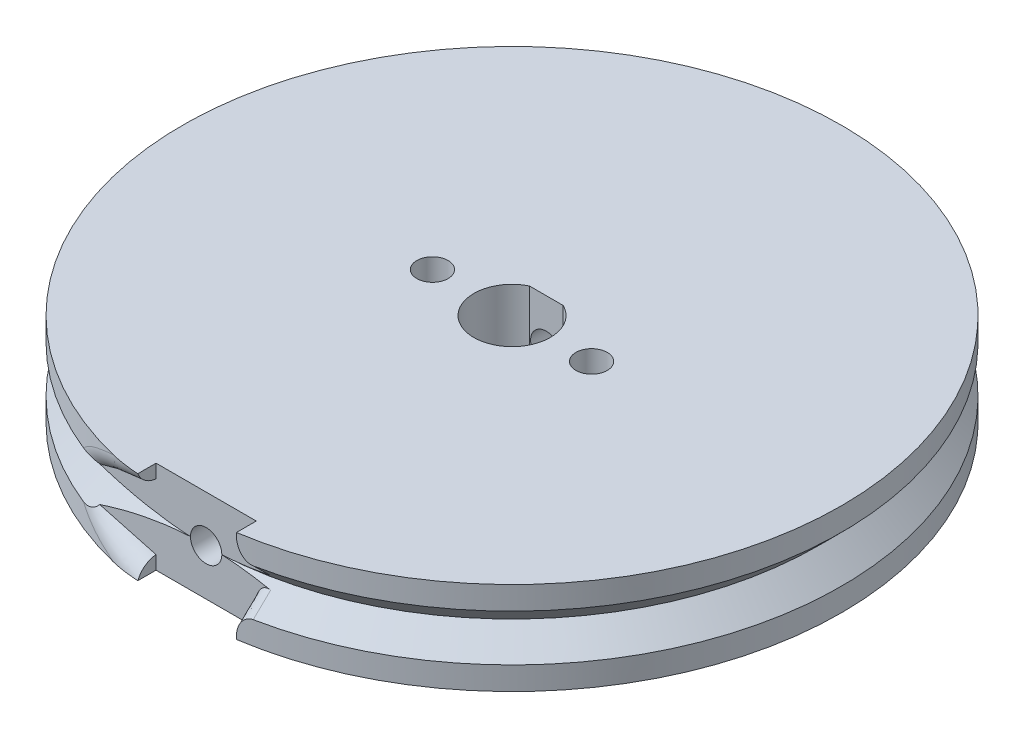
SolidWorks part; units mm, degrees
material "6061 Alloy"
ref_plane "Front Plane" through (0, 0, 0) normal (0, 0, 1) x (1, 0, 0)
ref_plane "Top Plane" through (0, 0, 0) normal (0, 1, 0) x (1, 0, 0)
ref_plane "Right Plane" through (0, 0, 0) normal (1, 0, 0) x (0, 0, -1)
ref_axis "Axis1" through (0, 0, 0) along (0, 1, 0)
sketch "Sketch2" plane through (0, 0, 0) normal (0, 0, 1) x (1, 0, 0)
  line L0 (0, 0) -> (0, 7.4)
  line L1 (0, 0) -> (0, 69.0457) construction
  line L2 (0, 7.4) -> (-26.3, 7.4)
  line L3 (-26.3, 7.4) -> (-26.3, 5.5586)
  line L4 (-26.3, 5.5586) -> (-24.4414, 3.7)
  line L5 (-24.4414, 3.7) -> (-26.3, 1.8414)
  line L6 (-26.3, 1.8414) -> (-26.3, 0)
  line L7 (-26.3, 0) -> (0, 0)
  circle A0 centre (-25, 3.7) radius 0.395 construction
  point P12 (-10.0863, 2.1131)
  dimension "D1" = 0.79
  dimension "D2" = 90
  dimension "D3" = 7.4
  dimension "D4" = 25
  dimension "D5" = 1.3
revolve "Revolve1" add sketch "Sketch2" angle 360 about axis through (0, 0, 0) along (0, 1, 0)
sketch "Sketch3" plane through (0, 7.4, 0) normal (0, 1, 0) x (1, 0, 0)
  line L0 (-1.35, 2.735) -> (1.35, 2.735)
  arc A1 (-1.35, 2.735) -> (1.35, 2.735) centre (0, 0) ccw
  dimension "D1" = 3.05
  dimension "D2" = 2.7
extrude "Cut-Extrude1" cut sketch "Sketch3" against normal blind 10
ref_plane "Plane1" through (0, 0, -30) normal (0, 0, 1) x (1, 0, 0)
sketch "Sketch5" plane through (0, 0, -30) normal (0, 0, 1) x (1, 0, 0)
  line L0 (24.4414, 3.7) -> (-24.4414, 3.7) construction
  circle A0 centre (0, 3.7) radius 2.5
  dimension "D1" = 5
extrude "Cut-Extrude2" cut sketch "Sketch5" along normal blind 24.5
sketch "Sketch6" plane through (0, 0, -5.5) normal (0, 0, -1) x (-1, 0, 0)
  circle A0 centre (0, 3.7) radius 2.5 construction
  point P0 (0, 3.7)
  point P1 (0, 0)
  point P4 (0, 0)
hole_wizard "M3x0.5 Tapped Hole1" positions "Sketch7" profile "Sketch8" tap size "M3x0.5" standard "ANSI Metric" end condition up to next
sketch "Sketch7" plane through (0, 0, -5.5) normal (0, 0, -1) x (-1, 0, 0)
  point P0 (0, 3.7)
sketch "Sketch8" plane through (0, 3.7, -5.5) normal (1, 0, 0) x (0, 1, 0)
  line L0 (0, 0) -> (0, 2.765)
  line L1 (0, 2.765) -> (1.25, 2.765)
  line L2 (1.25, 2.765) -> (1.25, 0)
  line L5 (1.25, 0) -> (0, 0)
  line L11 (0, -6.35) -> (0, 107.95) construction
  dimension "Thru Tap Drill Dia." = 2.5
  dimension "Thru Tap Drill Depth" = 2.765
cosmetic thread "Hole Thread1" parameters "D2"=3
sketch "Sketch9" plane through (0, 7.4, 0) normal (0, 1, 0) x (1, 0, 0)
  line L0 (0, 0) -> (0, -29.6328) construction
  line L1 (4, -28.566) -> (-4, -28.566)
  line L2 (4, -28.566) -> (4, -24.4119)
  line L3 (4, -24.4119) -> (-4, -24.4119)
  line L4 (-4, -28.566) -> (-4, -24.4119)
  line L5 (-4, -25.0566) -> (-4, -23.3902) construction
  line L6 (-4, -24.1119) -> (-5.2915, -24.1119) construction
  arc A0 (-2.5, 24.3132) -> (2.5, 24.3132) centre (0, 0) ccw construction
  arc A1 (-2.5, 24.3132) -> (2.5, 24.3132) centre (0, 0) ccw construction
  point P7 (0, -24.4119)
  dimension "D1" = 8
  dimension "D2" = 0.3
extrude "Cut-Extrude3" cut sketch "Sketch9" against normal through all
sketch "Sketch10" plane through (0, 0, 24.4119) normal (0, 0, 1) x (1, 0, 0)
  line L0 (0, 7.4) -> (0, 0) construction
  line L1 (4, 7.4) -> (-4, 7.4) construction
  point P5 (0, 3.7)
hole_wizard "M3x0.5 Tapped Hole2" positions "Sketch11" profile "Sketch12" tap size "M3x0.5" standard "ANSI Metric"
sketch "Sketch11" plane through (0, 0, 24.4119) normal (0, 0, 1) x (1, 0, 0)
  point P0 (0, 3.7)
sketch "Sketch12" plane through (0, 3.7, 24.4119) normal (1, 0, 0) x (0, -1, 0)
  line L0 (0, 0) -> (0, 8.2511)
  line L1 (0, 8.2511) -> (1.25, 7.5)
  line L2 (1.25, 7.5) -> (1.25, 0)
  line L5 (1.25, 0) -> (0, 0)
  line L10 (0, 8.2511) -> (-1.25, 7.5) construction
  line L11 (0, -6.35) -> (0, 107.95) construction
  dimension "Tap Drill Dia." = 2.5
  dimension "Tap Drill Depth" = 7.5
  dimension "Drill Angle" = 118
cosmetic thread "Hole Thread6" parameters "D1"=6, "D2"=3
sketch "Sketch13" plane through (0, 7.4, 0) normal (0, 1, 0) x (1, 0, 0)
  line L0 (6.35, 0) -> (-6.35, 0) construction
  point P3 (0, 0)
  dimension "D1" = 12.7
hole_wizard "M3x0.5 Tapped Hole3" positions "Sketch14" profile "Sketch15" tap size "M3x0.5" standard "ANSI Metric" end condition through all
sketch "Sketch14" plane through (0, 7.4, 0) normal (0, 1, 0) x (1, 0, 0)
  point P0 (6.35, 0)
  point P3 (-6.35, 0)
sketch "Sketch15" plane through (6.35, 7.4, 0) normal (1, 0, 0) x (0, 0, 1)
  line L0 (0, 0) -> (0, 7.4)
  line L1 (0, 7.4) -> (1.25, 7.4)
  line L2 (1.25, 7.4) -> (1.25, 0)
  line L5 (1.25, 0) -> (0, 0)
  line L11 (0, -6.35) -> (0, 107.95) construction
  dimension "Thru Tap Drill Dia." = 2.5
  dimension "Thru Tap Drill Depth" = 7.4
cosmetic thread "Hole Thread4" parameters "D2"=3
cosmetic thread "Hole Thread5" parameters "D2"=3
sketch "Sketch16" plane through (0, 0, 24.4119) normal (0, 0, 1) x (1, 0, 0)
  line L0 (0, 7.4) -> (0, 0)
  line L1 (0, 0) -> (-10, 2.7)
  line L2 (-10, 2.7) -> (-10, 4.7)
  line L3 (-10, 4.7) -> (0, 7.4)
  line L5 (0, 3.7) -> (-12.4271, 3.7) construction
  point P4 (-10, 3.7)
  dimension "D1" = 10
  dimension "D2" = 2
extrude "Cut-Extrude4" cut sketch "Sketch16" along normal through all
fillet "Fillet2" radius 1.6 2 edges at (-5.4181, 5.9371, 25.7359) (-5.4181, 1.4629, 25.7359)
fillet "Fillet3" radius 1 2 edges
